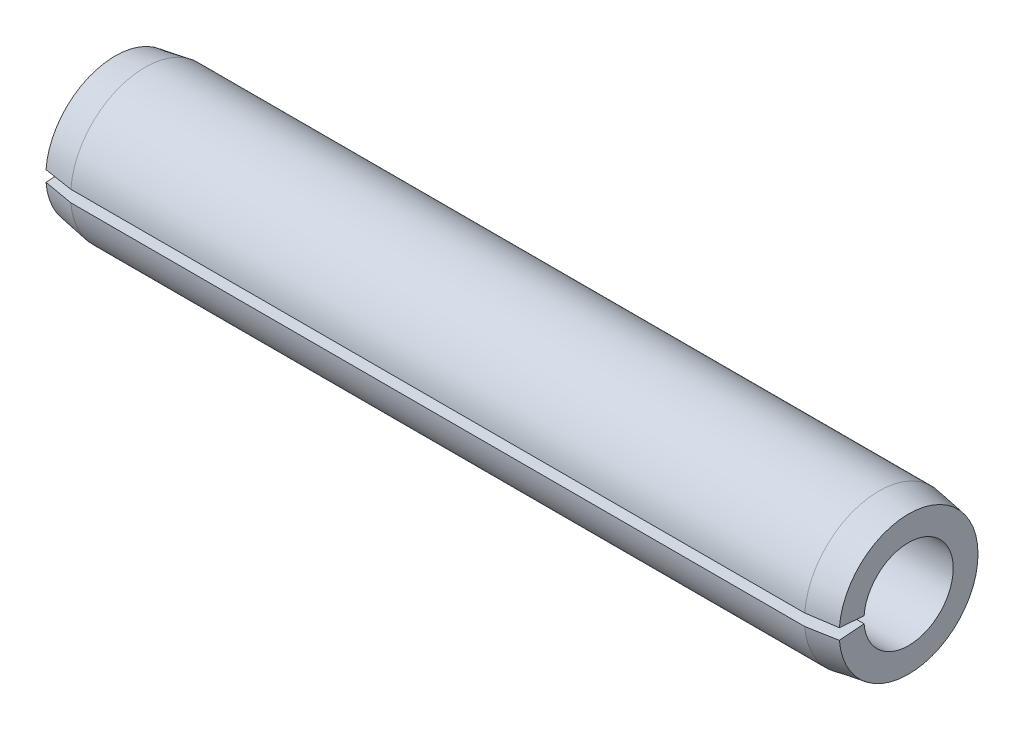
SolidWorks part; units mm, degrees
ref_plane "Plane1" through (0, 0, 0) normal (0, 0, 1) x (1, 0, 0)
ref_plane "Plane2" through (0, 0, 0) normal (0, 1, 0) x (1, 0, 0)
ref_plane "Plane3" through (0, 0, 0) normal (1, 0, 0) x (0, 0, -1)
sketch "Sketch1" plane through (0, 0, 0) normal (0, 0, 1) x (1, 0, 0)
  line L0 (-9.525, 0) -> (111.125, 0) construction
  line L1 (0, 5.715) -> (101.6, 5.715)
  line L2 (101.6, 5.715) -> (101.6, 8.89)
  line L3 (101.6, 8.89) -> (97.79, 9.525)
  line L4 (97.79, 9.525) -> (3.81, 9.525)
  line L5 (3.81, 9.525) -> (0, 8.89)
  line L7 (0, 8.89) -> (0, 5.715)
  dimension "Diameter" = 19.05
  dimension "Thickness" = 3.81
  dimension "Length" = 101.6
  dimension "Bottom_ch_len" = 3.81
  dimension "Top_ch_dia" = 17.78
  dimension "Top_ch_len" = 3.81
revolve "Base-Revolve" add sketch "Sketch1" angle 360 about L0
sketch "Sketch2" plane through (0, 0, 0) normal (-1, 0, 0) x (0, -1, 0)
  line L0 (0, 0) -> (0.7623, 9.6856)
  line L1 (0, -3.175) -> (0, 12.7) construction
  line L2 (0, 0) -> (-0.7623, 9.6856)
  arc A0 (0.7623, 9.6856) -> (-0.7623, 9.6856) centre (0, 0) ccw
  dimension "D1" = 9.7155
extrude "Gap" cut sketch "Sketch2" against normal through all
equation "\"D1@Sketch2\" = \"Diameter@Sketch1\" * 0.51"
equation "' \"Bottom_ch_dia@Sketch1\" = \"Diameter@Sketch1\" -  ( \"Thickness@Sketch1\" / 2 ) "
equation "' \"Bottom_ch_dia@Sketch1\" = \"Diameter@Sketch1\" -  ( \"Thickness@Sketch1\" / 2 )"
equation "' \"Top_ch_dia@Sketch1\" = \"Bottom_ch_dia@Sketch1\""
equation "' \"Top_ch_len@Sketch1\" = \"Bottom_ch_len@Sketch1\""
equation "\"Bottom_ch_len@Sketch1\" = \"Top_ch_len@Sketch1\""
